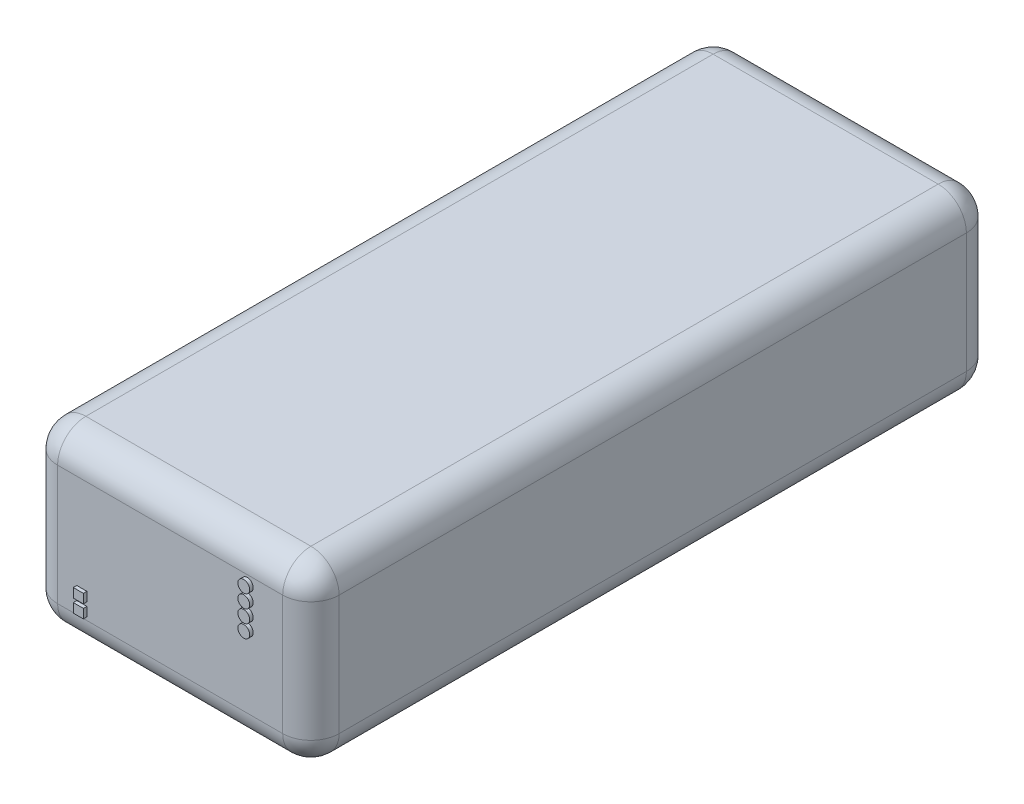
SolidWorks part; units mm, degrees
ref_plane "Front Plane" through (0, 0, 0) normal (0, 0, 1) x (1, 0, 0)
ref_plane "Top Plane" through (0, 0, 0) normal (0, 1, 0) x (1, 0, 0)
ref_plane "Right Plane" through (0, 0, 0) normal (1, 0, 0) x (0, 0, -1)
sketch "Sketch1" plane through (0, 0, 0) normal (0, 1, 0) x (1, 0, 0)
  line L1 (-60.8598, 65.7472) -> (-20.9602, 65.7472)
  line L2 (-60.8598, 65.7472) -> (-60.8598, -31.152)
  line L3 (-60.8598, -31.152) -> (-20.9602, -31.152)
  line L4 (-20.9602, 65.7472) -> (-20.9602, -31.152)
extrude "Boss-Extrude1" add sketch "Sketch1" along normal blind 25
fillet "Fillet4" radius 4 8 edges at (-40.91, 0, 31.152) (-20.9602, 0, -17.2976) (-40.91, 0, -65.7472) (-60.8598, 0, -17.2976) (-40.91, 25, -65.7472) (-20.9602, 25, -17.2976) (-40.91, 25, 31.152) (-60.8598, 25, -17.2976)
fillet "Fillet5" radius 4 12 edges at (-59.6882, 23.8284, -64.5756) (-59.6882, 1.1716, -64.5756) (-22.1317, 23.8284, -64.5756) (-22.1317, 1.1716, -64.5756) (-22.1317, 23.8284, 29.9804) (-22.1317, 1.1716, 29.9804) (-59.6882, 23.8284, 29.9804) (-59.6882, 1.1716, 29.9804) (-60.8598, 12.5, -65.7472) (-20.9602, 12.5, -65.7472) (-20.9602, 12.5, 31.152) (-60.8598, 12.5, 31.152)
ref_plane "Plane1" through (0, 0, 20.6) normal (0, 0, 1) x (1, 0, 0)
sketch "Sketch9" plane through (-20.9602, 0, 0) normal (1, 0, 0) x (0, 0, -1)
  spline S0 degree 3 poles (-17.3616, 9.136) (-52.093, -0.2177) (-85.172, 20.5717) (-120.0814, 15.2709) knots 0 0 0 0 1 1 1 1
sketch "Sketch10" plane through (0, 0, 0) normal (0, -1, 0) x (1, 0, 0)
  spline S0 degree 3 poles (-32.0354, 5.7815) (-38.7118, 42.6229) (-1.5302, 63.5317) (-6.7213, 99.754) knots 0 0 0 0 1 1 1 1
curve "Curve1"
sketch "Sketch11" plane through (0, 0, 31.152) normal (0, 0, 1) x (1, 0, 0)
  line L0 (-54.1421, 5.7451) -> (-52.7167, 5.7451)
  line L1 (-54.1421, 7.5918) -> (-52.7167, 7.5918)
  line L2 (-54.1421, 7.5918) -> (-54.1421, 6.2959)
  line L3 (-54.1421, 6.2959) -> (-52.7167, 6.2959)
  line L4 (-52.7167, 7.5918) -> (-52.7167, 6.2959)
  line L5 (-54.1421, 5.7451) -> (-54.1421, 4.4492)
  line L6 (-54.1421, 4.4492) -> (-52.7167, 4.4492)
  line L7 (-52.7167, 5.7451) -> (-52.7167, 4.4492)
  circle A0 centre (-29.9765, 19.8239) radius 0.8366
  circle A1 centre (-29.9765, 17.9541) radius 0.8366
  circle A2 centre (-29.9765, 14.2981) radius 0.8366
  circle A3 centre (-29.9765, 16.1447) radius 0.8366
extrude "Boss-Extrude2" add sketch "Sketch11" along normal blind 0.5
